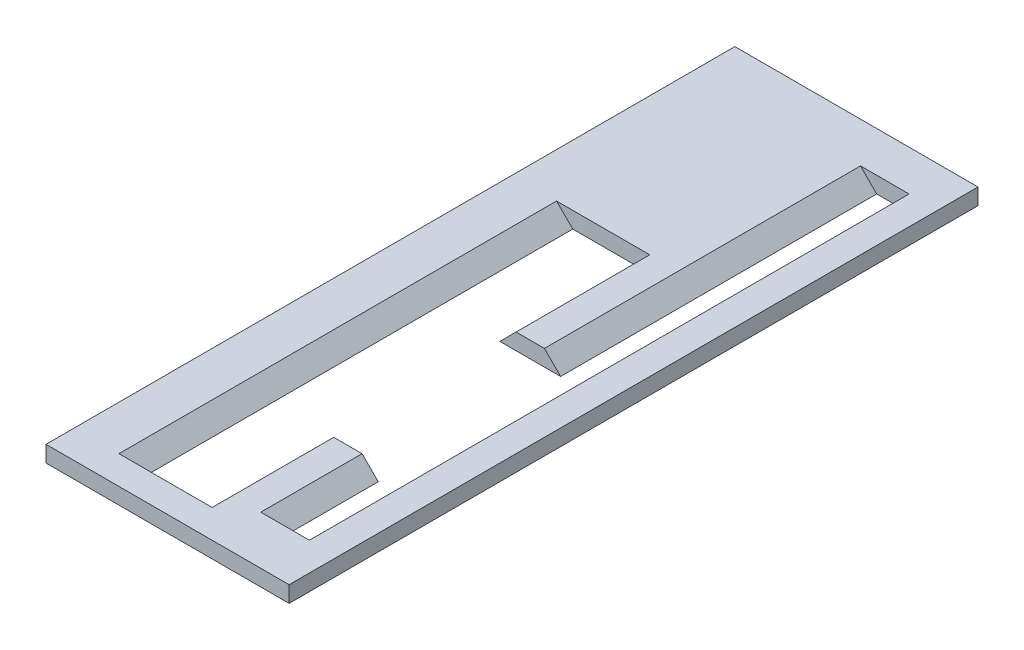
SolidWorks part; units mm, degrees
ref_plane "Płaszczyzna przednia" through (0, 0, 0) normal (0, 0, 1) x (1, 0, 0)
ref_plane "Płaszczyzna górna" through (0, 0, 0) normal (0, 1, 0) x (1, 0, 0)
ref_plane "Płaszczyzna prawa" through (0, 0, 0) normal (1, 0, 0) x (0, 0, -1)
sketch "Szkic1" plane through (0, 0, 0) normal (0, 0, 1) x (1, 0, 0)
  line L0 (-11.5, 2) -> (-7.5, -2)
  line L1 (-22.5, 2) -> (22.5, 2)
  line L2 (-22.5, 2) -> (-22.5, -2)
  line L3 (-22.5, -2) -> (22.5, -2)
  line L4 (22.5, 2) -> (22.5, -2)
  line L5 (-22.5, 2) -> (22.5, -2) construction
  line L6 (-22.5, -2) -> (22.5, 2) construction
  line L7 (0, 0) -> (0, 4.7316) construction
  line L8 (11.5, 2) -> (7.5, -2)
  point P0 (0, 0)
  dimension "D1" = 4
  dimension "D2" = 45
  dimension "D3" = 15
  dimension "D4" = 45
extrude "Dodanie-wyciągnięcie1" add sketch "Szkic1" against normal blind 110 contours L2 L3 L0 L1 | L1 L8 L3 L4 region at (-15.9487, -0.1026, 0) region at (15.9487, -0.1026, 0)
sketch "Szkic2" plane through (0, -2, 0) normal (0, -1, 0) x (1, 0, 0)
  line L0 (22.5, -110) -> (22.5, 0) construction
  line L1 (-22.5, 0) -> (22.5, 0)
  line L2 (-22.5, 0) -> (-22.5, 5)
  line L3 (-22.5, 5) -> (22.5, 5)
  line L4 (22.5, 0) -> (22.5, 5)
  line L6 (-22.5, -110) -> (22.5, -110)
  line L7 (-22.5, -110) -> (-22.5, -115)
  line L8 (-22.5, -115) -> (22.5, -115)
  line L9 (22.5, -110) -> (22.5, -115)
  point P5 (0, 0)
  point P13 (36.7157, -122.9786)
  point P14 (0, 0)
  point P15 (22.5, -110)
  dimension "D1" = 5
  dimension "D2" = 5
extrude "Dodanie-wyciągnięcie2" add sketch "Szkic2" against normal up to vertex (4 mm away) up to point (22.5, 2, -110)
sketch "Szkic4" plane through (0, 2, 0) normal (0, 1, 0) x (1, 0, 0)
  line L0 (-22.5, 55) -> (22.5, 55) construction
  line L1 (-22.5, 115) -> (-22.5, -5) construction
  line L2 (22.5, 115) -> (22.5, -5) construction
  line L4 (5, 70) -> (40, 70)
  line L5 (5, 70) -> (5, 40)
  line L6 (5, 40) -> (40, 40)
  line L7 (40, 70) -> (40, 40)
  line L8 (5, 70) -> (40, 40) construction
  line L9 (5, 40) -> (40, 70) construction
  dimension "D1" = 30
  dimension "D2" = 35
extrude "Wytnij-wyciągnięcie1" cut sketch "Szkic4" against normal blind 10
sketch "Szkic5" plane through (0, -2, 0) normal (0, -1, 0) x (1, 0, 0)
  line L0 (-22.5, -115) -> (22.5, -115) construction
  line L1 (22.5, 5) -> (37.5, 5)
  line L2 (22.5, 5) -> (22.5, -165)
  line L3 (22.5, -165) -> (37.5, -165)
  line L4 (37.5, 5) -> (37.5, -165)
  line L6 (22.5, -165) -> (-22.5, -165)
  line L7 (22.5, -165) -> (22.5, -115)
  line L8 (22.5, -115) -> (-22.5, -115)
  line L9 (-22.5, -165) -> (-22.5, -115)
  line M10 (22.5, -40) -> (22.5, 5)
  line M13 (-22.5, -115) -> (22.5, -115)
  line M14 (22.5, -115) -> (22.5, -70)
  dimension "D1" = 15
  dimension "D2" = 50
extrude "Dodanie-wyciągnięcie3" add sketch "Szkic5" against normal up to vertex (4 mm away) contours L9 L6 L2 M13 | L4 L1 L2 L3 M10 M14 region at (30, -2, -80) region at (0, -2, -140) up to point (-22.5, 2, -115)
sketch "Szkic6" plane through (0, 2, 0) normal (0, 1, 0) x (1, 0, 0)
  line L0 (37.5, -5) -> (37.5, 165) construction
  line L1 (22.5, 155) -> (26.5, 155)
  line L2 (22.5, 155) -> (22.5, 7)
  line L3 (22.5, 7) -> (26.5, 7)
  line L4 (26.5, 155) -> (26.5, 7)
  line L5 (37.5, -5) -> (-22.5, -5) construction
  line L6 (11.5, 110) -> (-11.5, 110) construction
  dimension "D1" = 15
  dimension "D2" = 4
  dimension "D3" = 12
  dimension "D4" = 45
extrude "Wytnij-wyciągnięcie2" cut sketch "Szkic6" against normal blind 10
chamfer "Sfazowanie1" distance 4 angle 45 3 edges at (22.5, 2, -23.5) (22.5, 2, -112.5) (26.5, 2, -81)
sketch "Szkic7" plane through (0, 0, 0) normal (0, 0, -1) x (-1, 0, 0)
  line L4 (-11.5, 2) -> (-7.5, -2)
  line L5 (-7.5, -2) -> (7.5, -2)
  line L6 (7.5, -2) -> (11.5, 2)
  line L7 (11.5, 2) -> (-11.5, 2)
  line L8 (-11.5, 2) -> (-7.5, -2)
  line L9 (-7.5, -2) -> (7.5, -2)
  line L10 (7.5, -2) -> (11.5, 2)
  line L11 (11.5, 2) -> (-11.5, 2)
  dimension "D1" = 0
extrude "Dodanie-wyciągnięcie4" add sketch "Szkic7" along normal blind 2
sketch "Szkic9" plane through (0, -2, 0) normal (0, -1, 0) x (1, 0, 0)
  line L0 (7.5, -40) -> (7.5, -2) construction
  line L1 (7.5, -32) -> (22.5, -32)
  line L2 (7.5, -32) -> (7.5, -77)
  line L3 (7.5, -77) -> (22.5, -77)
  line L4 (22.5, -32) -> (22.5, -77)
  line L5 (22.5, -70) -> (22.5, -155) construction
  line L7 (7.5, -2) -> (-7.5, -2) construction
  dimension "D1" = 30
  dimension "D2" = 45
extrude "Wytnij-wyciągnięcie3" cut sketch "Szkic9" against normal blind 80 contours L2 L1 L4 L3
